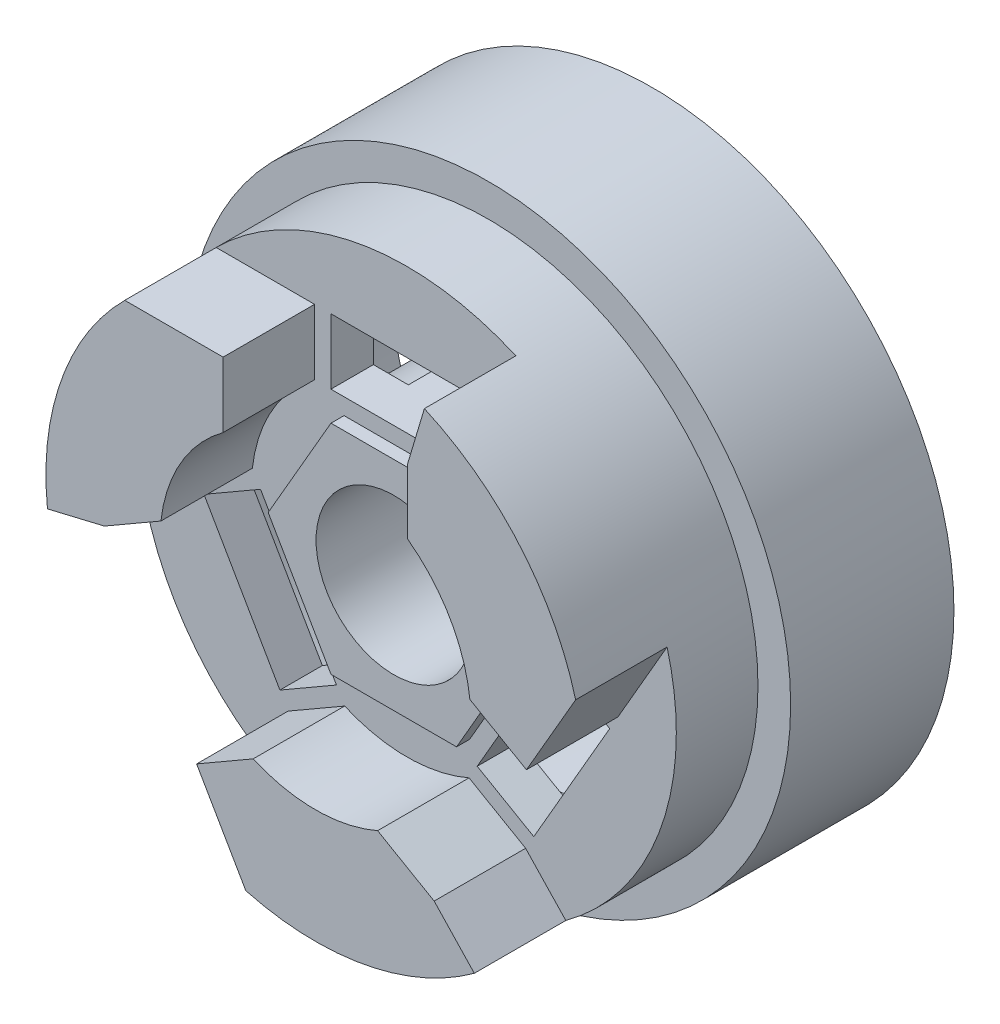
SolidWorks part; units mm, degrees
ref_plane "Front Plane" through (0, 0, 0) normal (0, 0, 1) x (1, 0, 0)
ref_plane "Top Plane" through (0, 0, 0) normal (0, 1, 0) x (1, 0, 0)
ref_plane "Right Plane" through (0, 0, 0) normal (1, 0, 0) x (0, 0, -1)
sketch "Sketch1" plane through (0, 0, 0) normal (0, 0, 1) x (1, 0, 0)
  circle A0 centre (0, 0) radius 9.25
  circle A1 centre (0, 0) radius 7.95
  dimension "D1" = 18.5
  dimension "D2" = 1.3
extrude "Boss-Extrude1" add sketch "Sketch1" along normal blind 5
sketch "Sketch3" plane through (0, 0, 0) normal (0, 0, 1) x (1, 0, 0)
  circle A0 centre (0, 0) radius 8.25
  circle A1 centre (0, 0) radius 6.95
  dimension "D1" = 16.5
  dimension "D2" = 1.3
extrude "Boss-Extrude2" add sketch "Sketch3" along normal blind 2.5 and the other way blind 1 from surface starting at face at (9.25, 0, 5)
sketch "Sketch4" plane through (0, 0, 7.5) normal (0, 0, 1) x (1, 0, 0)
  circle A1 centre (0, 0) radius 8.25
  circle A2 centre (0, 0) radius 8.25
  dimension "D1" = 0
extrude "Boss-Extrude3" add sketch "Sketch4" against normal blind 1.3
sketch "Sketch5" plane through (0, 0, 6.2) normal (0, 0, -1) x (-1, 0, 0)
  circle A0 centre (0, 0) radius 2.38
  circle A1 centre (0, 0) radius 4.03
  dimension "D1" = 4.76
  dimension "D2" = 1.65
extrude "Boss-Extrude4" add sketch "Sketch5" along normal offset from surface (6.7 mm away) 0.5 up to face at (9.25, 0, 0) offset beyond the face yes
extrude "Cut-Extrude1" cut sketch "Sketch5<2>" against normal through all contours A0
sketch "Sketch5<2>" plane through (0, 0, 6.2) normal (0, 0, -1) x (-1, 0, 0) same geometry as "Sketch5"
sketch "Sketch6" plane through (0, 0, 7.5) normal (0, 0, 1) x (1, 0, 0)
  line L1 (-2.325, 5.83) -> (2.325, 5.83)
  line L2 (-2.325, 5.83) -> (-2.325, 3.83)
  line L3 (-2.325, 3.83) -> (2.325, 3.83)
  line L4 (2.325, 5.83) -> (2.325, 3.83)
  circle A1 centre (0, 0) radius 2.38 construction
  point P6 (0, 3.83)
  dimension "D1" = 2
  dimension "D2" = 4.65
  dimension "D3" = 1.45
extrude "Cut-Extrude2" cut sketch "Sketch6" against normal through all
pattern_circular "CirPattern1" count 3 over 360 about axis through (0, 0, 7.5) along (0, 0, 1) of "Cut-Extrude2"
sketch "Sketch7" plane through (0, 0, 7.5) normal (0, 0, 1) x (1, 0, 0)
  line L0 (-2.1544, -3.9285) -> (-4.4794, 0.0985) construction
  line L1 (-1.9226, -3.33) -> (1.9226, -3.33)
  line L2 (1.9226, -3.33) -> (3.8452, 0)
  line L3 (3.8452, 0) -> (1.9226, 3.33)
  line L4 (1.9226, 3.33) -> (-1.9226, 3.33)
  line L5 (-1.9226, 3.33) -> (-3.8452, 0)
  line L6 (-3.8452, 0) -> (-1.9226, -3.33)
  circle A0 centre (0, 0) radius 3.33 construction
  circle A1 centre (0, 0) radius 2.38 construction
  circle A2 centre (0, 0) radius 2.38
  dimension "D1" = 0.5
extrude "Boss-Extrude5" add sketch "Sketch7" along normal offset from surface (0.4 mm away) 8.4 up to face at (2.38, 0, -0.5)
sketch "Sketch8" plane through (0, 0, 7.5) normal (0, 0, 1) x (1, 0, 0)
  line L0 (3.6364, -5.3615) -> (1.9044, -4.3615)
  line L1 (-1.9044, -4.3615) -> (-3.6364, -5.3615)
  line L2 (-3.8864, -4.9285) -> (-2.1544, -3.9285) construction
  line L3 (2.1544, -3.9285) -> (3.8864, -4.9285) construction
  line L4 (-3.6364, -5.3615) -> (-2.1303, -7.9702)
  line L5 (-3.6364, -5.3615) -> (-3.8864, -4.9285) construction
  line L7 (-6.2114, -0.9015) -> (-3.8864, -4.9285) construction
  line L8 (4.866, -6.6622) -> (3.6364, -5.3615)
  arc A0 (-1.9044, -4.3615) -> (1.9044, -4.3615) centre (0, 0) ccw
  arc A1 (4.866, -6.6622) -> (-2.1303, -7.9702) centre (0, 0) cw
  circle A3 centre (0, 0) radius 9.25 construction
  dimension "D3" = 1
  dimension "D1" = 0.5
  dimension "D2" = 0.5
extrude "Boss-Extrude6" add sketch "Sketch8" along normal blind 2.8
pattern_circular "CirPattern2" count 3 over 360 about axis through (0, 0, 5) along (0, 0, 1) of "Boss-Extrude6"
